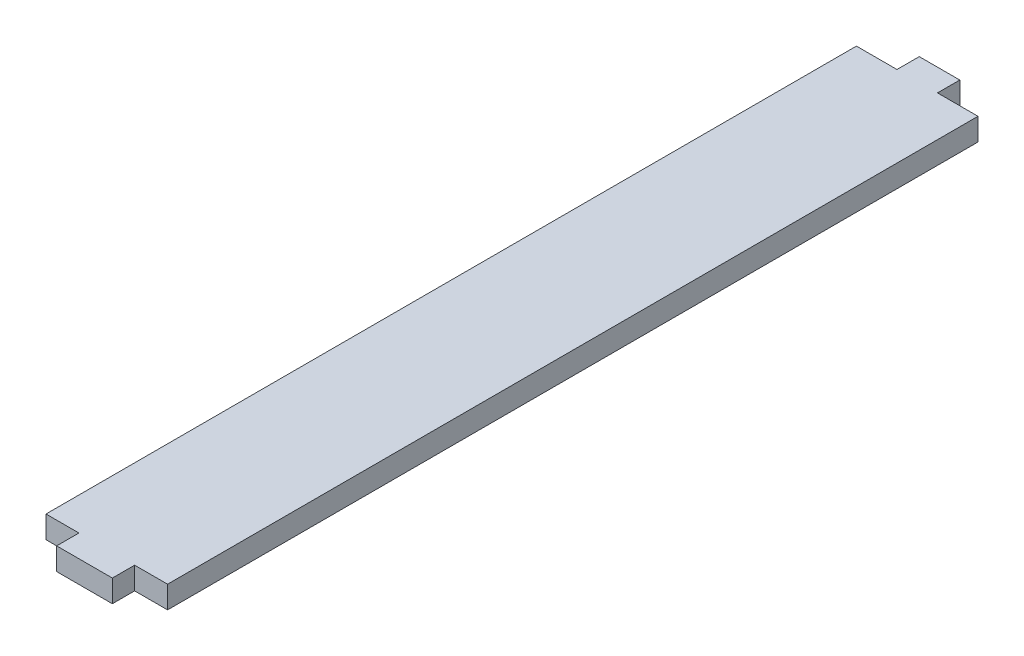
SolidWorks part; units mm, degrees
ref_plane "Front Plane" through (0, 0, 0) normal (0, 0, 1) x (1, 0, 0)
ref_plane "Top Plane" through (0, 0, 0) normal (0, 1, 0) x (1, 0, 0)
ref_plane "Right Plane" through (0, 0, 0) normal (1, 0, 0) x (0, 0, -1)
sketch "Sketch1" plane through (0, 0, 0) normal (0, 1, 0) x (1, 0, 0)
  line L0 (77.2861, -37.0625) -> (91.0361, -37.0625)
  line L1 (69.1611, 168.4375) -> (99.1611, 168.4375)
  line L2 (69.1611, 168.4375) -> (69.1611, -31.5625)
  line L3 (69.1611, -31.5625) -> (99.1611, -31.5625)
  line L4 (99.1611, 168.4375) -> (99.1611, -31.5625)
  line L5 (79.1611, 162.9375) -> (89.1611, 162.9375)
  line L6 (79.1611, 162.9375) -> (79.1611, 173.9375)
  line L7 (79.1611, 173.9375) -> (89.1611, 173.9375)
  line L8 (89.1611, 162.9375) -> (89.1611, 173.9375)
  line L9 (79.1611, 162.9375) -> (89.1611, 173.9375) construction
  line L10 (79.1611, 173.9375) -> (89.1611, 162.9375) construction
  line L11 (77.2861, -37.0625) -> (77.2861, -26.0625)
  line L12 (77.2861, -26.0625) -> (91.0361, -26.0625)
  line L13 (91.0361, -37.0625) -> (91.0361, -26.0625)
  line L14 (77.2861, -37.0625) -> (91.0361, -26.0625) construction
  line L15 (77.2861, -26.0625) -> (91.0361, -37.0625) construction
  point P4 (84.1611, 168.4375)
  point P9 (84.1611, -31.5625)
  dimension "D1" = 200
  dimension "D2" = 30
  dimension "D3" = 10
  dimension "D4" = 5.5
  dimension "D5" = 5.5
extrude "Boss-Extrude1" add sketch "Sketch1" along normal blind 5.5 contours L13 L3 L4 L1 L8 L5 L6 L2 L11 L12 | L0 L13 L12 L11 | L5 L8 L7 L6 region at (84.1611, 0, -68.7792)
equation "\"mat\"=\"mat@V1.assembly\""
equation "\"D4@Sketch1\"=\"mat\""
equation "\"D1@Boss-Extrude1\"=\"mat\""
equation "\"D5@Sketch1\" = \"mat\""
